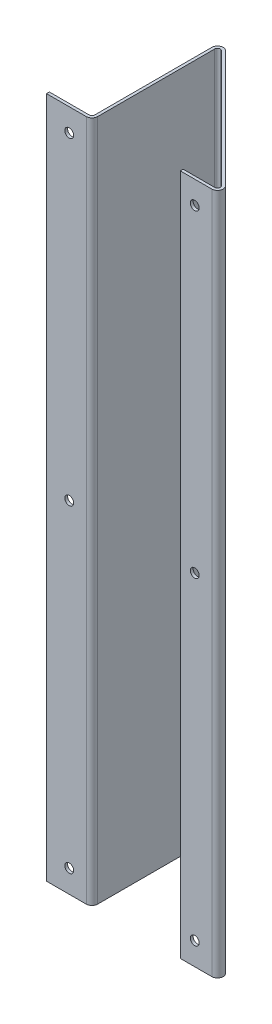
SolidWorks part; units mm, degrees
material "6061-T6 (SS)"
ref_plane "Front Plane" through (0, 0, 0) normal (0, 0, 1) x (1, 0, 0)
ref_plane "Top Plane" through (0, 0, 0) normal (0, 1, 0) x (1, 0, 0)
ref_plane "Right Plane" through (0, 0, 0) normal (1, 0, 0) x (0, 0, -1)
sketch "Sketch1" plane through (0, 0, 0) normal (0, 1, 0) x (1, 0, 0)
  line L0 (0, 1.5875) -> (22.225, 1.5875)
  line L1 (23.8125, 3.175) -> (23.8125, 68.5349)
  line L2 (29.2326, 70.7799) -> (94.5924, 5.4201)
  line L3 (92.3474, 0) -> (74.7454, 0)
  line L4 (0, 0) -> (22.225, 0)
  line L9 (25.4, 3.175) -> (25.4, 68.5349)
  line L10 (28.11, 69.6574) -> (93.4699, 4.2975)
  line L11 (92.3474, 1.5875) -> (74.7454, 1.5875)
  line L14 (92.3474, 0) -> (74.7454, 0)
  line L15 (29.2326, 70.7799) -> (94.5924, 5.4201)
  line L16 (23.8125, 3.175) -> (23.8125, 68.5349)
  line L17 (0, 1.5875) -> (22.225, 1.5875)
  line L20 (74.7454, 1.5875) -> (74.7454, 0)
  line L21 (0, 1.5875) -> (0, 0)
  arc A0 (92.3474, 0) -> (94.5924, 5.4201) centre (92.3474, 3.175) ccw
  arc A1 (22.225, 1.5875) -> (23.8125, 3.175) centre (22.225, 3.175) ccw
  arc A3 (22.225, 0) -> (25.4, 3.175) centre (22.225, 3.175) ccw
  arc A6 (28.11, 69.6574) -> (25.4, 68.5349) centre (26.9875, 68.5349) ccw
  arc A8 (29.2326, 70.7799) -> (23.8125, 68.5349) centre (26.9875, 68.5349) ccw
  arc A10 (92.3474, 1.5875) -> (93.4699, 4.2975) centre (92.3474, 3.175) ccw
  point P0 (23.8125, 76.2)
  point P3 (0, 0)
  point P4 (0, 0)
  dimension "D5" = 3.175
  dimension "D7" = 17.602
  dimension "D9" = 76.2
  dimension "D8" = 3.175
  dimension "D10" = 22.225
  dimension "D12" = 45
  dimension "D1" = 1.5875
  dimension "D2" = 3.175
  dimension "D4" = 1.5875
  dimension "D6" = 1.5875
  dimension "D3" = 1.5875
  dimension "D14" = 1.5875
extrude "Boss-Extrude1" add sketch "Sketch1" along normal mid plane 381 contours A10 L11 L20 L3 A0 L2 A8 L1 A1 L0 L21 L4 A3 L9 A6 L10 region at (11.1125, 0, -0.3931)
sketch "Sketch2" plane through (0, 0, -1.5875) normal (0, 0, -1) x (-1, 0, 0)
  line L0 (0, 190.5) -> (-22.225, 190.5) construction
  line L1 (0, 190.5) -> (0, -190.5) construction
  line L3 (-95.5224, 190.5) -> (-95.5224, -190.5) construction
  line L4 (-92.3474, 190.5) -> (-74.7454, 190.5) construction
  circle A0 centre (-12.7, 177.8) radius 2.4892
  circle A1 centre (-12.7, 0) radius 2.4892
  circle A2 centre (-12.7, -177.8) radius 2.4892
  circle A3 centre (-82.8224, 177.8) radius 2.4892
  circle A4 centre (-82.8224, 0) radius 2.4892
  circle A5 centre (-82.8224, -177.8) radius 2.4892
  dimension "D1" = 4.9784
  dimension "D5" = 4.9784
  dimension "D2" = 12.7
  dimension "D3" = 12.7
  dimension "D6" = 12.7
  dimension "D7" = 12.7
  dimension "D4" = 3
  dimension "D8" = 3
extrude "Cut-Extrude1" cut sketch "Sketch2" against normal through all
